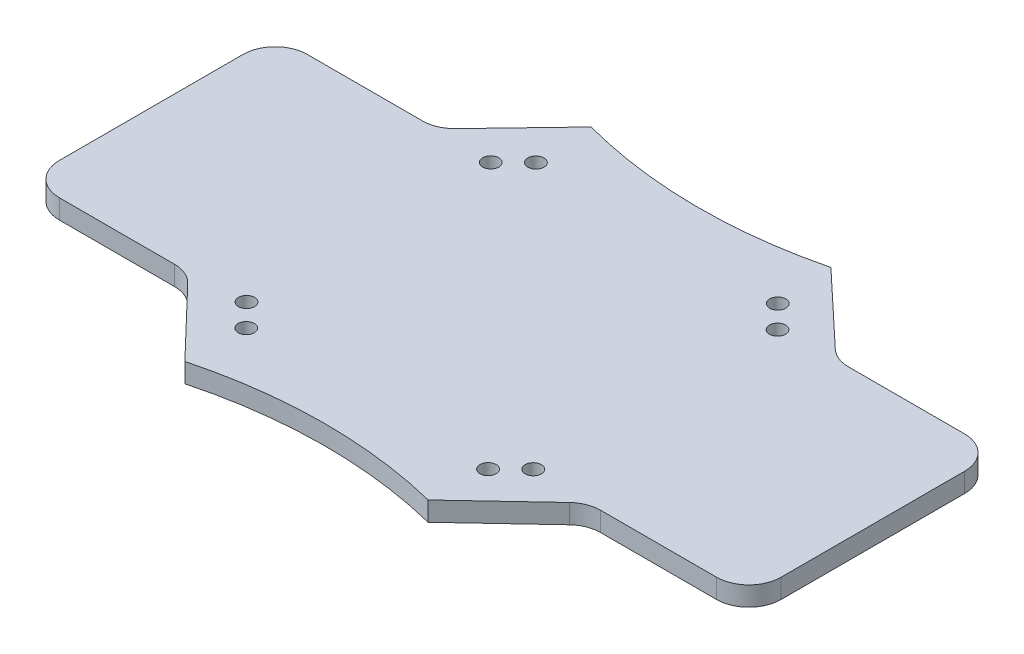
SolidWorks part; units mm, degrees
ref_plane "前视基准面" through (0, 0, 0) normal (0, 0, 1) x (1, 0, 0)
ref_plane "上视基准面" through (0, 0, 0) normal (0, 1, 0) x (1, 0, 0)
ref_plane "右视基准面" through (0, 0, 0) normal (1, 0, 0) x (0, 0, -1)
sketch "草图1" plane through (0, 0, 0) normal (0, 1, 0) x (1, 0, 0)
  line L0 (-112, -28.5) -> (-112, 28.5)
  line L1 (-102, 38.5) -> (-66.2677, 38.5)
  line L2 (-59.0474, 41.5814) -> (-38.5, 63.025)
  line L3 (36.4657, 62.5) -> (59.1131, 41.2134)
  line L4 (65.9619, 38.5) -> (102, 38.5)
  line L5 (0, -27.7495) -> (0, 27.7495) construction
  line L6 (-142.0403, 0) -> (142.0403, 0) construction
  line L7 (112, 28.5) -> (112, -28.5)
  line L8 (65.9619, -38.5) -> (102, -38.5)
  line L9 (36.4657, -62.5) -> (59.1131, -41.2134)
  line L10 (-59.0474, -41.5814) -> (-38.5, -63.025)
  line L11 (-102, -38.5) -> (-66.2677, -38.5)
  arc A0 (-38.5, 63.025) -> (36.4657, 62.5) centre (0, 208) ccw
  arc A1 (102, 38.5) -> (112, 28.5) centre (102, 28.5) cw
  arc A2 (59.1131, 41.2134) -> (65.9619, 38.5) centre (65.9619, 48.5) ccw
  arc A3 (-66.2677, 38.5) -> (-59.0474, 41.5814) centre (-66.2677, 48.5) ccw
  arc A4 (-112, 28.5) -> (-102, 38.5) centre (-102, 28.5) cw
  arc A5 (-112, -28.5) -> (-102, -38.5) centre (-102, -28.5) ccw
  arc A6 (-66.2677, -38.5) -> (-59.0474, -41.5814) centre (-66.2677, -48.5) cw
  arc A7 (59.1131, -41.2134) -> (65.9619, -38.5) centre (65.9619, -48.5) cw
  arc A8 (102, -38.5) -> (112, -28.5) centre (102, -28.5) ccw
  arc A9 (-38.5, -63.025) -> (36.4657, -62.5) centre (0, -208) cw
  point P0 (-112, -38.5)
  point P8 (-112, 0)
  point P19 (112, 38.5)
  point P22 (62, 38.5)
  point P25 (-62, 38.5)
  point P28 (-112, 38.5)
  point P44 (112, 0)
  point P45 (-62, -38.5)
  point P46 (62, -38.5)
  point P47 (112, -38.5)
  dimension "D1" = 150
  dimension "D10" = 10
  dimension "D2" = 208
  dimension "D3" = 50
  dimension "D4" = 38.5
  dimension "D5" = 24
  dimension "D6" = 112
  dimension "D7" = 38.5
  dimension "D8" = 112
  dimension "D9" = 50
extrude "凸台-拉伸1" add sketch "草图1" along normal mid plane 6 contours A0 L3 A2 L4 A1 L7 A8 L8 A7 L9 A9 L10 A6 L11 A5 L0 A4 L1 A3 L2
ref_axis "基准轴1" through (0, -142.0403, 0) along (0, 1, 0)
sketch "草图2" plane through (0, 3, 0) normal (0, 1, 0) x (1, 0, 0)
  line L2 (0, 0) -> (44.9143, 37.4876) construction
  line L3 (0, 0) -> (37.9403, 44.5325) construction
  line L4 (-142.0403, 0) -> (142.0403, 0) construction
  circle A2 centre (0, 0) radius 58.5031 construction
  circle A3 centre (37.9403, 44.5325) radius 2.5
  circle A4 centre (44.9143, 37.4876) radius 2.5
  circle A5 centre (0, 0) radius 58.5031 construction
  point P8 (0, 0)
  dimension "D4" = 5
  dimension "D5" = 5
  dimension "D2" = 39.85
  dimension "D3" = 9.72
extrude "切除-拉伸2" cut sketch "草图2" against normal through all
pattern_circular "阵列(圆周)1" count 4 over 360 about axis through (0, -142.0403, 0) along (0, 1, 0) of "切除-拉伸2"
